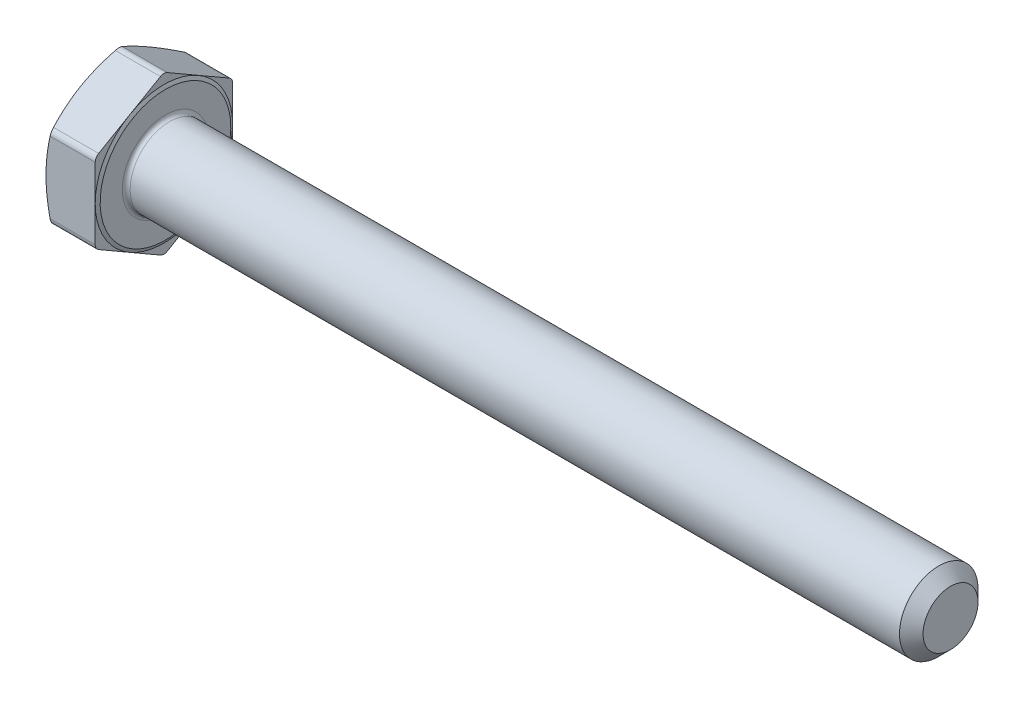
SolidWorks part; units mm, degrees
ref_plane "Front Plane" through (0, 0, 0) normal (0, 0, 1) x (1, 0, 0)
ref_plane "Top Plane" through (0, 0, 0) normal (0, 1, 0) x (1, 0, 0)
ref_plane "Right Plane" through (0, 0, 0) normal (1, 0, 0) x (0, 0, -1)
sketch "Sketch1" plane through (0, 0, 0) normal (0, 0, 1) x (1, 0, 0)
  line L0 (0, 0) -> (63.5, 0) construction
  line L1 (0, 0) -> (-4.3656, 0) construction
  line L2 (0, 5.5562) -> (0, -5.5562) construction
  line L3 (-4.3656, 5.5562) -> (-4.3656, -5.5563) construction
  line L4 (63.5, 3.175) -> (63.5, -3.175) construction
  line L8 (62.23, 3.175) -> (63.5, 3.175) construction
  point P8 (62.23, 0)
  point P11 (59.055, -3.175)
  point P12 (1.27, 0)
  dimension "Head Height" = 4.3656
  dimension "Head Width" = 11.1125
  dimension "Length" = 63.5
  dimension "Thread Size" = 6.35
  dimension "D1" = 4.445
  dimension "Thread Pitch" = 1.27
  dimension "D2" = 1.27
sketch "Sketch2" plane through (0, 0, 0) normal (1, 0, 0) x (0, 0, -1)
  circle A0 centre (0, 0) radius 3.175
extrude "Boss-Extrude1" add sketch "Sketch2" along normal up to vertex (63.5 mm away) up to point (63.5, 3.175, 0)
sketch "Sketch3" plane through (0, 0, 0) normal (-1, 0, 0) x (0, 0, 1)
  line L0 (0, 6.4158) -> (0, 0) construction
  line L1 (0, 6.4158) -> (-5.5563, 3.2079)
  line L2 (-5.5563, 3.2079) -> (-5.5563, -3.2079)
  line L3 (-5.5563, -3.2079) -> (0, -6.4158)
  line L4 (0, -6.4158) -> (5.5562, -3.2079)
  line L5 (5.5562, -3.2079) -> (5.5562, 3.2079)
  line L6 (5.5562, 3.2079) -> (0, 6.4158)
  circle A0 centre (0, 0) radius 5.5562 construction
extrude "Boss-Extrude2" add sketch "Sketch3" along normal up to vertex (4.3656 mm away) up to point (-4.3656, 5.5562, 0)
sketch "Sketch5" plane through (-4.3656, 0, 0) normal (-1, 0, 0) x (0, 0, 1)
  circle A0 centre (0, 0) radius 5.5562 construction
  circle A1 centre (0, 0) radius 5.5562 construction
  circle A2 centre (0, 0) radius 5.0006
  dimension "D1" = 0.5556
extrude "Cut-Extrude1" cut sketch "Sketch5" against normal up to vertex (4.3656 mm away) draft 65 flip side to cut up to point (0, 0, 0)
sketch "Sketch11" plane through (-4.3656, 0, 0) normal (-1, 0, 0) x (0, 0, 1)
  line L0 (0, 3.9449) -> (0, 2.4448) construction
  line L1 (0.2223, 3.9449) -> (0.2223, 2.4448)
  line L2 (-0.2222, 3.9449) -> (-0.2222, 2.4448)
  arc A0 (0.2223, 3.9449) -> (-0.2222, 3.9449) centre (0, 3.9449) ccw
  arc A1 (-0.2222, 2.4448) -> (0.2223, 2.4448) centre (0, 2.4448) ccw
  circle A2 centre (0, 0) radius 4.1672 construction
  circle A3 centre (0, 0) radius 2.2225 construction
  point P3 (0, 3.1948)
  dimension "D1" = 8.3344
  dimension "D2" = 4.445
  dimension "D3" = 0.4445
extrude "Boss-Extrude5" add sketch "Sketch11" along normal blind 0.0635
fillet "Fillet5" radius 0.0635 4 edges at (-4.4291, 3.1948, 0.2223) (-4.4291, 2.2225, 0) (-4.4291, 3.1948, -0.2222) (-4.4291, 4.1672, 0)
pattern_circular "CirPattern1" count 6 over 360 about axis through (0, 0, 0) along (-1, 0, 0) of "Boss-Extrude5", "Fillet5" reverse direction yes
fillet "Fillet7" radius 0.5556 6 edges at (-1.8529, -6.4158, 0) (-1.8529, -3.2079, -5.5563) (-1.8529, 3.2079, -5.5563) (-1.8529, 6.4158, 0) (-1.8529, -3.2079, 5.5562) (-1.8529, 3.2079, 5.5562)
chamfer "Chamfer1" distance 0.9525 angle 45 1 edges at (63.5, 0, -3.175)
sketch "Sketch15" plane through (0, 0, 0) normal (0, 0, 1) x (1, 0, 0)
  line L0 (0, 5.2839) -> (-0.127, 5.5562)
  line L1 (0, 5.5562) -> (0, -5.5562) construction
  line L2 (-0.127, 5.5562) -> (-0.127, 6.4158)
  line L3 (-0.127, 6.4158) -> (0, 6.4158)
  line L4 (0, 6.4158) -> (0, 5.2839)
  dimension "D1" = 0.127
  dimension "D2" = 25
revolve "Cut-Revolve1" cut sketch "Sketch15" angle 360 about L1
fillet "Fillet4" radius 0.3175 1 edges at (0, 0, 3.175)
sketch "Reference Sketch1" plane through (0, 0, 0) normal (1, 0, 0) x (0, 0, -1)
  line L1 (0, 6.4158) -> (-5.5563, 3.2079)
  line L2 (-5.5563, 3.2079) -> (-5.5563, -3.2079)
  line L3 (-5.5563, -3.2079) -> (0, -6.4158)
  line L4 (0, -6.4158) -> (5.5563, -3.2079)
  line L5 (5.5563, -3.2079) -> (5.5563, 3.2079)
  line L6 (5.5563, 3.2079) -> (0, 6.4158)
  circle A0 centre (0, 0) radius 5.5563 construction
  circle A1 centre (0, 0) radius 5.5562
sketch "Sketch12" [suppressed] plane through (9.525, 0, 0) normal (1, 0, 0) x (0, 0, -1)
  circle A1 centre (0, 0) radius 3.175
ref_plane "Plane2" [suppressed] through (1.27, 0, 0) normal (1, 0, 0) x (0, 0, -1)
split "Split1" [suppressed] bodies to split 126 116
curve "Helix/Spiral2" [suppressed] parameters "Pitch"=1.27
sketch "Sketch13" [suppressed] plane through (0, 0, 0) normal (0, 0, 1) x (1, 0, 0)
  line L0 (9.4456, 3.3125) -> (10.0806, 2.2126) construction
  line L1 (10.0806, 2.2126) -> (10.7156, 3.3125) construction
  line L2 (10.7156, 3.3125) -> (9.4456, 3.3125) construction
  line L3 (10.0806, 2.2126) -> (10.0806, 2.3501) construction
  line L4 (9.525, 3.175) -> (10.6362, 3.175)
  line L5 (10.0806, 3.175) -> (10.0806, 3.3125) construction
  line L6 (10.6362, 3.175) -> (10.16, 2.3501)
  line L7 (10.16, 2.3501) -> (10.0012, 2.3501)
  line L8 (10.0012, 2.3501) -> (9.525, 3.175)
  line L9 (8.255, 3.175) -> (9.525, 3.175) construction
  dimension "D1" = 0.1588
sweep "Cut-Sweep1" [suppressed] cut profiles "Sketch13" path "Helix/Spiral2"
sketch "Sketch14" [suppressed] plane through (1.27, 0, 0) normal (1, 0, 0) x (0, 0, -1)
  circle A1 centre (0, 0) radius 3.175
  circle A2 centre (0, 0) radius 3.175
  dimension "D1" = 0
extrude "Boss-Extrude4" [suppressed] add sketch "Sketch14" along normal through all draft 50
equation "\"D1@Sketch11\"=\"Head Width@Sketch1\" * 0.75"
equation "\"D2@Sketch11\"=\"Head Width@Sketch1\"*0.4"
equation "\"D3@Sketch11\"=\"Head Width@Sketch1\" * .04"
equation "\"D3@Helix/Spiral2\"=\"Length@Sketch1\" + \"Thread Pitch@Sketch1\""
equation "\"D1@Chamfer1\"=\"Thread Pitch@Sketch1\"*0.750"
equation "\"D1@Sketch1\"=\"Thread Pitch@Sketch1\"*3.5"
equation "\"Pitch@Helix/Spiral2\"=\"Thread Pitch@Sketch1\""
equation "\"D1@Sketch13\"=\"Thread Pitch@Sketch1\"*0.125"
equation "\"D1@Sketch5\"=\"Head Width@Sketch1\"*0.05"
equation "\"D1@Fillet4\"=\"Thread Size@Sketch1\"*0.05"
equation "\"D2@Sketch1\"=\"Thread Pitch@Sketch1\""
equation "\"D1@Fillet7\"=\"Head Width@Sketch1\"*0.05"
